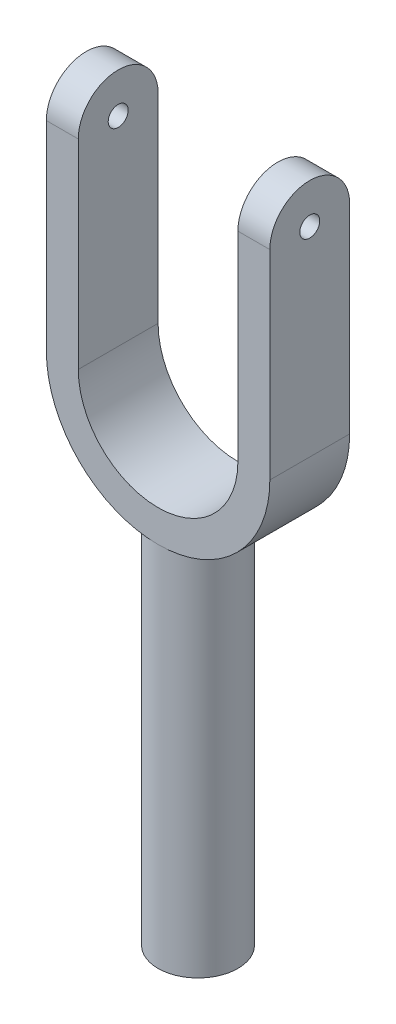
SolidWorks part; units mm, degrees
material "PE haute densité"
ref_plane "Plan de face" through (0, 0, 0) normal (0, 0, 1) x (1, 0, 0)
ref_plane "Plan de dessus" through (0, 0, 0) normal (0, 1, 0) x (1, 0, 0)
ref_plane "Plan de droite" through (0, 0, 0) normal (1, 0, 0) x (0, 0, -1)
sketch "Esquisse4" plane through (0, 0, 0) normal (0, 0, 1) x (1, 0, 0)
  line L0 (0, 0) -> (0, 12.607) construction
  line L4 (-70, 0) -> (-70, 150)
  line L5 (-70, 150) -> (-50, 150)
  line L6 (-50, 0) -> (-50, 150)
  line L7 (70, 0) -> (70, 150)
  line L8 (70, 150) -> (50, 150)
  line L9 (50, 0) -> (50, 150)
  arc A0 (-50, 0) -> (50, 0) centre (0, 0) ccw
  arc A1 (-70, 0) -> (70, 0) centre (0, 0) ccw
  dimension "D1" = 50
  dimension "D2" = 70
  dimension "D3" = 20
  dimension "D4" = 150
  dimension "D5" = 150
extrude "Boss.-Extru.1" add sketch "Esquisse4" along normal mid plane 50
fillet "Congé2" 2 edges at (-60, 150, 25) (-60, 150, -25) type full round first side face at (0, 60, 25) second side face at (0, 60, -25) middle face at (-60, 150, 0)
fillet "Congé3" 2 edges at (60, 150, 25) (60, 150, -25) type full round first side face at (0, 53.75, 25) second side face at (0, 53.75, -25) middle face at (60, 150, 0)
ref_plane "Plan1" through (0, -300, 0) normal (0, 1, 0) x (1, 0, 0)
sketch "Esquisse6" plane through (0, -300, 0) normal (0, 1, 0) x (1, 0, 0)
  circle A0 centre (0, 0) radius 25
  dimension "D1" = 50
extrude "Boss.-Extru.3" add sketch "Esquisse6" along normal up to surface (230 mm away) up to face at (0, -35, 0)
sketch "Esquisse7" plane through (70, 0, 0) normal (1, 0, 0) x (0, 0, -1)
  line L0 (-25, 125) -> (25, 125) construction
  circle A0 centre (0, 125) radius 6.25
  dimension "D1" = 12.5
extrude "Enlèv. mat.-Extru.1" cut sketch "Esquisse7" against normal through all
equation "\"R_i\"= 50"
equation "\"R_e\"= \"R_i\" * 1.4"
equation "\"Thickness\"= \"R_i\" * 0.4"
equation "\"Length\"= \"R_i\" * 3"
equation "\"D1@Esquisse4\"=\"R_i\""
equation "\"D2@Esquisse4\"=\"R_e\""
equation "\"D3@Esquisse4\"=\"Thickness\""
equation "\"D4@Esquisse4\"=\"Length\""
equation "\"D5@Esquisse4\"=\"Length\""
equation "\"D1@Boss.-Extru.1\"=\"R_i\""
equation "\"Thickness_bossage\"= \"R_i\""
equation "\"Plan1_dist\"= \"R_i\" * 4"
equation "\"Cylinder_radius\"= \"R_i\""
equation "\"D1@Esquisse6\"=\"Cylinder_radius\""
equation "\"D1@Esquisse7\"=\"R_i\"/4"
